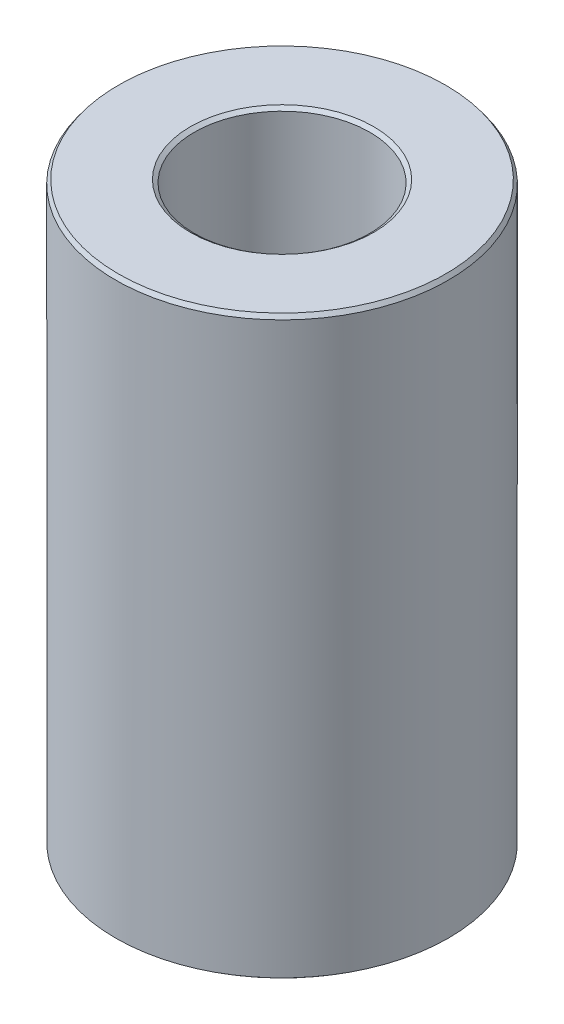
SolidWorks part; units mm, degrees
ref_plane "Front Plane" through (0, 0, 0) normal (0, 0, 1) x (1, 0, 0)
ref_plane "Top Plane" through (0, 0, 0) normal (0, 1, 0) x (1, 0, 0)
ref_plane "Right Plane" through (0, 0, 0) normal (1, 0, 0) x (0, 0, -1)
sketch "Sketch1" plane through (0, 0, 0) normal (0, 1, 0) x (1, 0, 0)
  circle A0 centre (0, 0) radius 57.5
  dimension "SLEEVE_OD" = 115
extrude "Boss-Extrude1" add sketch "Sketch1" along normal blind 199.2262
sketch "Sketch2" plane through (0, 0, 0) normal (0, 1, 0) x (1, 0, 0)
  circle A0 centre (0, 0) radius 30.3162
  dimension "BORE_D" = 60.6324
extrude "Cut-Extrude1" cut sketch "Sketch2" along normal through all
chamfer "Chamfer1" distance 1.3527 angle 35.976 4 edges at (0, 199.2262, 30.3162) (0, 0, 30.3162) (0, 0, 57.5) (0, 199.2262, 57.5) first distance on face at (0, 199.2262, 30.3162) first distance on face at (0, 0, 30.3162) first distance on face at (0, 199.2262, 57.5)
